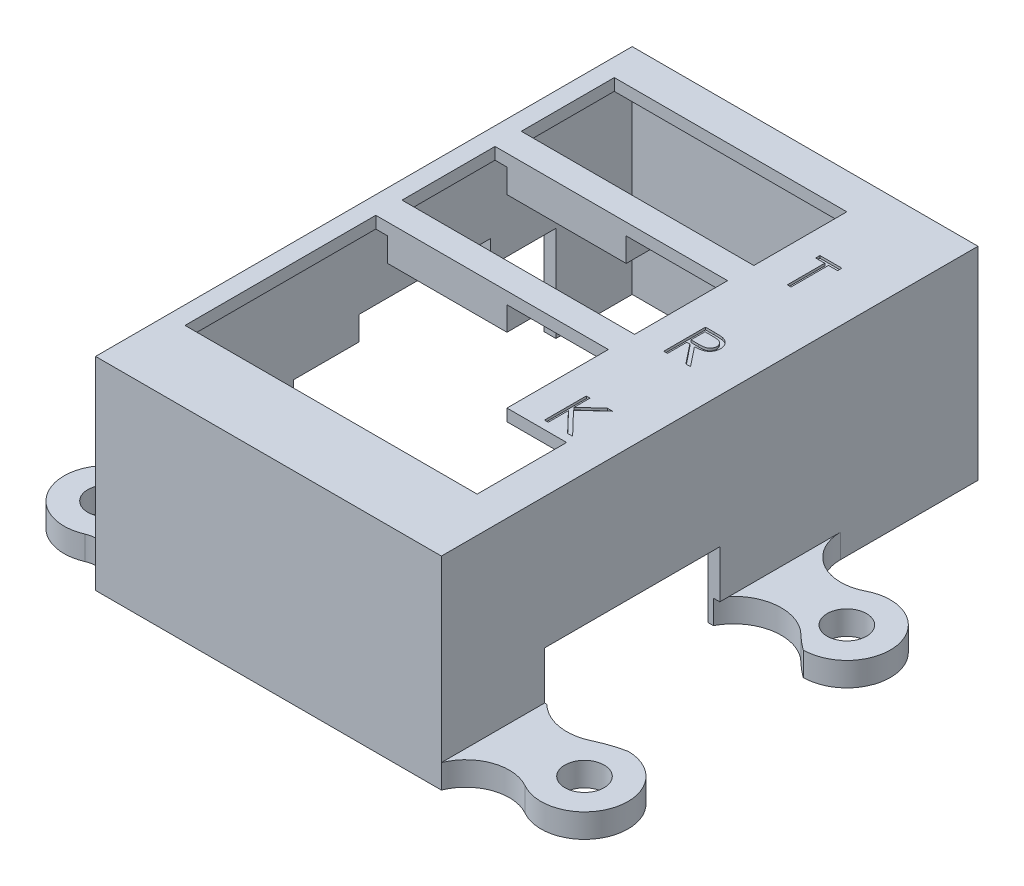
SolidWorks part; units mm, degrees
material "Polyetheretherketone (PEEK)"
ref_plane "Front Plane" through (0, 0, 0) normal (0, 0, 1) x (1, 0, 0)
ref_plane "Top Plane" through (0, 0, 0) normal (0, 1, 0) x (1, 0, 0)
ref_plane "Right Plane" through (0, 0, 0) normal (1, 0, 0) x (0, 0, -1)
sketch "Sketch1" plane through (0, 0, 0) normal (0, 1, 0) x (1, 0, 0)
  line L1 (-14.5, 22.5) -> (14.5, 22.5)
  line L2 (-14.5, 22.5) -> (-14.5, -22.5)
  line L3 (-14.5, -22.5) -> (14.5, -22.5)
  line L4 (14.5, 22.5) -> (14.5, -22.5)
  line L5 (-14.5, 22.5) -> (14.5, -22.5) construction
  line L6 (-14.5, -22.5) -> (14.5, 22.5) construction
  point P0 (0, 0)
  dimension "D1" = 45
  dimension "D2" = 29
extrude "Boss-Extrude1" add sketch "Sketch1" along normal blind 15
sketch "Sketch2" plane through (0, 15, 0) normal (0, 1, 0) x (1, 0, 0)
  line L0 (-13, 9.5) -> (-13, 1.7)
  line L1 (-13, 19.5) -> (6.5, 19.5)
  line L2 (-13, 19.5) -> (-13, 11.7)
  line L3 (-13, 11.7) -> (6.5, 11.7)
  line L4 (14.5, -22.5) -> (14.5, 22.5)
  line L5 (14.5, 22.5) -> (-14.5, 22.5)
  line L6 (-14.5, 22.5) -> (-14.5, -22.5)
  line L7 (-14.5, -22.5) -> (14.5, -22.5)
  line L8 (14.5, -22.5) -> (14.5, 22.5) construction
  line L9 (14.5, 22.5) -> (-14.5, 22.5) construction
  line L10 (-14.5, 22.5) -> (-14.5, -22.5) construction
  line L11 (-14.5, -22.5) -> (14.5, -22.5) construction
  line L12 (6.5, 19.5) -> (6.5, 11.7)
  line L13 (-13, 9.5) -> (6.5, 9.5)
  line L14 (6.5, 9.5) -> (6.5, 1.7)
  line L15 (-13, 1.7) -> (6.5, 1.7)
  line L16 (-13, -0.5) -> (-13, -8.3)
  line L17 (-13, -0.5) -> (6.5, -0.5)
  line L18 (6.5, -0.5) -> (6.5, -8.3)
  line L20 (-13, -8.3) -> (-13, -9.7)
  line L21 (6.5, -9) -> (11.5, -9)
  line L22 (-13, -9.7) -> (-13, -16.5)
  line L23 (-13, -16.5) -> (11.5, -16.5)
  line L24 (11.5, -9) -> (11.5, -16.5)
  line L25 (6.5, -8.3) -> (6.5, -9)
  line L28 (-13, -8.3) -> (6.5, -8.3) [skipped]
  dimension "D2" = 7.8
  dimension "D3" = 19.5
  dimension "D4" = 3
  dimension "D5" = 3
  dimension "D7" = 2.2
  dimension "D8" = 6.8
  dimension "D9" = 24.5
  dimension "D10" = 3
  dimension "D11" = 0.7
  dimension "D12" = 16
  dimension "D1" = 0
  dimension "D6" = 3
shell "Shell2" thickness 1 removed face at (0, 0, 0)
extrude "Cut-Extrude2" cut sketch "Sketch2" against normal through all
sketch "Sketch3" plane through (0, 14, 0) normal (0, -1, 0) x (1, 0, 0)
  line L4 (13.5, -21.5) -> (13.5, 21.5)
  line L5 (13.5, 21.5) -> (-13.5, 21.5)
  line L6 (-13.5, 21.5) -> (-13.5, -21.5)
  line L7 (-13.5, -21.5) -> (13.5, -21.5)
  line L8 (13.5, -21.5) -> (13.5, 21.5) construction
  line L9 (13.5, 21.5) -> (-13.5, 21.5) construction
  line L10 (-13.5, 21.5) -> (-13.5, -21.5) construction
  line L11 (-13.5, -21.5) -> (13.5, -21.5) construction
  line L12 (-13, -19.5) -> (6.5, -19.5)
  line L13 (-13, -11.7) -> (-13, -19.5)
  line L14 (6.5, -11.7) -> (-13, -11.7)
  line L15 (6.5, -19.5) -> (6.5, -11.7)
  line L16 (-13, -19.5) -> (6.5, -19.5) construction
  line L17 (-13, -11.7) -> (-13, -19.5) construction
  line L18 (6.5, -11.7) -> (-13, -11.7) construction
  line L19 (6.5, -19.5) -> (6.5, -11.7) construction
  line L20 (6.5, -9.5) -> (6.5, -1.7)
  line L21 (-13, -9.5) -> (6.5, -9.5)
  line L22 (-13, -1.7) -> (-13, -9.5)
  line L23 (6.5, -1.7) -> (-13, -1.7)
  line L24 (6.5, -9.5) -> (6.5, -1.7) construction
  line L25 (-13, -9.5) -> (6.5, -9.5) construction
  line L26 (-13, -1.7) -> (-13, -9.5) construction
  line L27 (6.5, -1.7) -> (-13, -1.7) construction
  line L30 (-13, 0.5) -> (6.5, 0.5)
  line L31 (-13, 16.5) -> (-13, 0.5)
  line L32 (11.5, 16.5) -> (-13, 16.5)
  line L33 (11.5, 9) -> (11.5, 16.5)
  line L34 (6.5, 9) -> (11.5, 9)
  line L35 (6.5, 0.5) -> (6.5, 9)
  line L36 (-13, 0.5) -> (6.5, 0.5) construction
  line L37 (-13, 16.5) -> (-13, 0.5) construction
  line L38 (11.5, 16.5) -> (-13, 16.5) construction
  line L39 (11.5, 9) -> (11.5, 16.5) construction
  line L40 (6.5, 9) -> (11.5, 9) construction
  line L41 (6.5, 0.5) -> (6.5, 9) construction
  line L45 (-12, 0.5) -> (-2, 0.5)
  line L46 (-12, 0.5) -> (-12, -1.7)
  line L47 (-12, -1.7) -> (-2, -1.7)
  line L48 (-2, 0.5) -> (-2, -1.7)
  line L49 (-12, -9.5) -> (-2, -9.5)
  line L50 (-12, -9.5) -> (-12, -11.7)
  line L51 (-12, -11.7) -> (-2, -11.7)
  line L52 (-2, -9.5) -> (-2, -11.7)
  dimension "D1" = 0
  dimension "D5" = 2
  dimension "D6" = 10
  dimension "D7" = 2
extrude "Boss-Extrude2" add sketch "Sketch3" along normal blind 2
sketch "cutout" plane through (-14.5, 0, 0) normal (-1, 0, 0) x (0, 0, 1)
  line L0 (-22.5, 0) -> (22.5, 0) construction
  line L1 (-15.1, 6) -> (6.9, 6)
  line L2 (-15.1, 6) -> (-15.1, 0)
  line L3 (-15.1, 0) -> (6.9, 0)
  line L4 (-22.5, 0) -> (22.5, 0)
  line L5 (22.5, 0) -> (22.5, 15)
  line L6 (22.5, 15) -> (-22.5, 15)
  line L7 (-22.5, 15) -> (-22.5, 0)
  line L8 (-22.5, 0) -> (22.5, 0) construction
  line L9 (22.5, 0) -> (22.5, 15) construction
  line L10 (22.5, 15) -> (-22.5, 15) construction
  line L11 (-22.5, 15) -> (-22.5, 0) construction
  line L12 (6.9, 6) -> (6.9, 0)
  line L14 (-9.6, 6) -> (1.4, 6)
  line L15 (-9.6, 6) -> (-9.6, 8)
  line L16 (-9.6, 8) -> (1.4, 8)
  line L17 (1.4, 6) -> (1.4, 8)
  point P14 (-4.1, 8)
  point P15 (-4.1, 6)
  line M8 (-22.5, 0) -> (22.5, 0)
  dimension "D2" = 11
  dimension "D3" = 6
  dimension "D4" = 7.4
  dimension "D5" = 22
  dimension "D6" = 2
  dimension "D1" = 0
extrude "Cut-Extrude3" cut sketch "cutout" against normal up to surface (1 mm away) contours L1 L17 L16 L15 | L12 L1 L2 M8 region at (-14.5, 3, -4.1) region at (-14.5, 7, -4.1) up to face at (-13.5, 7, 0)
sketch "Sketch5" plane through (0, 0, 0) normal (0, -1, 0) x (1, 0, 0)
  line L0 (0, 0) -> (0, 21.5) construction
  line L1 (-14.5, 6.9) -> (-14.5, 10.2084)
  line L3 (-14.5, 22.5) -> (14.5, 22.5)
  line L4 (13.5, -21.5) -> (-13.5, -21.5) construction
  line L5 (-13.5, -15.1) -> (-14.5, -15.1) construction
  line L6 (-13.5, -21.5) -> (-13.5, -15.1) construction
  line L7 (-14.5, -22.5) -> (-14.5, -15.1) construction
  line L8 (-13.5, -15.1) -> (-14.5, -15.1)
  line L9 (-13.5, -21.5) -> (-13.5, -15.1)
  line L10 (-14.5, -22.5) -> (-14.5, -15.1)
  line L11 (21.5, -0.85) -> (13.5, -0.85)
  line L12 (-14.5, 6.9) -> (-13.5, 6.9)
  line L13 (-13.5, 6.9) -> (-13.5, 21.5)
  line L14 (-13.5, 21.5) -> (13.5, 21.5)
  line L15 (13.5, 21.5) -> (13.5, -21.5)
  line L16 (13.5, -21.5) -> (-13.5, -21.5)
  line L17 (-13.5, -21.5) -> (-13.5, -15.1)
  line L18 (-13.5, -15.1) -> (-14.5, -15.1)
  line L19 (-14.5, -15.1) -> (-14.5, -22.5)
  line L20 (-14.5, -22.5) -> (14.5, -22.5)
  line L21 (14.5, -22.5) -> (14.5, 22.5)
  line L22 (14.5, 22.5) -> (-14.5, 22.5)
  line L23 (-14.5, 22.5) -> (-14.5, 6.9)
  line L24 (-14.5, 6.9) -> (-13.5, 6.9)
  line L25 (-13.5, 6.9) -> (-13.5, 21.5)
  line L26 (-13.5, 21.5) -> (13.5, 21.5)
  line L27 (13.5, 21.5) -> (13.5, 13.85)
  line L28 (13.5, -21.5) -> (-13.5, -21.5)
  line L32 (-14.5, -22.5) -> (14.5, -22.5)
  line L33 (14.5, -22.5) -> (14.5, -10.9859)
  line L34 (14.5, 22.5) -> (-14.5, 22.5)
  line L35 (-14.5, 22.5) -> (-14.5, 6.9)
  line L36 (-11.5, 6.5) -> (8.5, 6.5)
  line L37 (-11.5, 6.5) -> (-11.5, -15.5)
  line L38 (-11.5, -15.5) -> (8.5, -15.5)
  line L39 (8.5, 6.5) -> (8.5, -15.5)
  line L40 (-11.5, 6.5) -> (8.5, -15.5) construction
  line L41 (-11.5, -15.5) -> (8.5, 6.5) construction
  line L42 (21.5, 13.85) -> (13.5, 13.85)
  line L43 (13.5, 21.5) -> (13.5, -21.5) construction
  line L44 (13.5, -0.85) -> (13.5, -21.5)
  circle A0 centre (21.5, 17.5) radius 1.65
  circle A1 centre (21.5, -4.5) radius 1.65
  circle A3 centre (-18.5, 17.5) radius 1.65
  circle A4 centre (-18.5, 17.5) radius 3.65
  circle A5 centre (21.5, 17.5) radius 3.65
  circle A6 centre (21.5, -4.5) radius 3.65
  arc A8 (-17.035, 20.8431) -> (-14.5, 22.5) centre (-16.309, 22.5) ccw
  arc A11 (-14.5, 10.2084) -> (-18.325, 13.8542) centre (-18.15, 10.2084) ccw
  arc A16 (19.825, -7.743) -> (14.5, -10.9859) centre (18.15, -10.9859) ccw
  circle A18 centre (-21.5, -4.5) radius 3.65 construction
  circle A19 centre (-21.5, -4.5) radius 1.65 construction
  arc A20 (14.5, 22.5) -> (19.6963, 20.6732) centre (17.8926, 23.8464) ccw
  point P54 (-1.5, -4.5)
  line M27 (-14.5, 6.9) -> (-13.5, 6.9)
  line M28 (-13.5, 6.9) -> (-13.5, 21.5)
  line M29 (-13.5, 21.5) -> (13.5, 21.5)
  line M30 (13.5, 21.5) -> (13.5, -21.5)
  line M31 (13.5, -21.5) -> (-13.5, -21.5)
  line M32 (-13.5, -21.5) -> (-13.5, -15.1)
  line M33 (-13.5, -15.1) -> (-14.5, -15.1)
  line M34 (-14.5, -15.1) -> (-14.5, -22.5)
  line M35 (-14.5, -22.5) -> (14.5, -22.5)
  line M36 (14.5, -22.5) -> (14.5, 22.5)
  line M37 (14.5, 22.5) -> (-14.5, 22.5)
  line M38 (-14.5, 22.5) -> (-14.5, 6.9)
  dimension "D1" = 0
  dimension "D2" = 3.3
  dimension "D3" = 3.3
  dimension "D4" = 7
  dimension "D5" = 5
  dimension "D6" = 22
  dimension "D9" = 20
  dimension "D10" = 4
  dimension "D11" = 5
  dimension "D12" = 27
  dimension "D13" = 43
  dimension "D14" = 5
  dimension "D15" = 6
  dimension "D8" = 15
  dimension "D16" = 17
extrude "Boss-Extrude3" add sketch "Sketch5" along normal blind 2 contours A4 A3 | A11 A8 A4 M38 | L26 L33 M38 M27 M28 M29 M30 M31 M32 M33 M34 M35 M36 M37 | A5 M36 | A5 A0 | L33 A16 A6 | A6 A1 | L42 M36 M37 M38 M27 M28 M29 M30 region at (-14.1707, 0, 8.5542) region at (-15.5429, 0, 12.9437) region at (-21.9878, 0, 18.1438) region at (16.4492, 0, 17.1799) region at (23.2837, 0, 20.5656) region at (14.1381, 0, -5.918) region at (16.43, 0, -4.3695) region at (24.0079, 0, -1.9921)
sketch "Sketch6" plane through (0, 15, 0) normal (0, 1, 0) x (1, 0, 0)
  line L3 (8.5, 11.7) -> (13.4782, 11.7) construction
  line L7 (8.5, 1.7) -> (12.8749, 1.7) construction
  line L11 (8.5, -8.3) -> (12.5892, -8.3) construction
  line L16 (6.5, 9.5) -> (-13, 9.5)
  line L17 (6.5, 1.7) -> (6.5, 9.5)
  line L18 (-13, 1.7) -> (6.5, 1.7)
  line L19 (-13, 9.5) -> (-13, 1.7)
  line L20 (6.5, 9.5) -> (-13, 9.5) construction
  line L21 (6.5, 1.7) -> (6.5, 9.5) construction
  line L22 (-13, 1.7) -> (6.5, 1.7) construction
  line L23 (-13, 9.5) -> (-13, 1.7) construction
  line L24 (-13, 19.5) -> (-13, 11.7)
  line L25 (6.5, 19.5) -> (-13, 19.5)
  line L26 (-13, -0.5) -> (-13, -16.5)
  line L27 (6.5, -0.5) -> (-13, -0.5)
  line L28 (6.5, -9) -> (6.5, -0.5)
  line L29 (11.5, -9) -> (6.5, -9)
  line L30 (11.5, -16.5) -> (11.5, -9)
  line L31 (-13, -16.5) -> (11.5, -16.5)
  line L32 (-13, -0.5) -> (-13, -16.5) construction
  line L33 (6.5, -0.5) -> (-13, -0.5) construction
  line L34 (6.5, -9) -> (6.5, -0.5) construction
  line L35 (11.5, -9) -> (6.5, -9) construction
  line L36 (11.5, -16.5) -> (11.5, -9) construction
  line L37 (-13, -16.5) -> (11.5, -16.5) construction
  line L38 (6.5, 11.7) -> (6.5, 19.5)
  line L39 (-13, 11.7) -> (6.5, 11.7)
  line L40 (-13, 19.5) -> (-13, 11.7) construction
  line L41 (6.5, 19.5) -> (-13, 19.5) construction
  line L42 (6.5, 11.7) -> (6.5, 19.5) construction
  line L43 (-13, 11.7) -> (6.5, 11.7) construction
  text T0 "T"
  text T1 "R"
  text T2 "K"
  dimension "D1" = 0
  dimension "D2" = 0
  dimension "D4" = 10
  dimension "D5" = 2
  dimension "D3" = 0
extrude "Cut-Extrude4" cut sketch "Sketch6" against normal blind 0.2
sketch "Sketch7" plane through (14.5, 0, 0) normal (1, 0, 0) x (0, 0, -1)
  line L1 (-13.85, 4) -> (0.85, 4)
  line L2 (-13.85, 4) -> (-13.85, 0)
  line L3 (-13.85, 0) -> (0.85, 0)
  line L4 (0.85, 4) -> (0.85, 0)
  line L8 (-22.5, 0) -> (-13.85, 0)
  line L9 (-13.85, 0) -> (0.85, 0)
  line L10 (0.85, 0) -> (10.9859, 0)
  line L11 (10.9859, 0) -> (10.9859, -2)
  line L12 (10.9859, -2) -> (22.5, -2)
  line L13 (22.5, -2) -> (22.5, 15)
  line L14 (22.5, 15) -> (-22.5, 15)
  line L15 (-22.5, 15) -> (-22.5, 0)
  line L16 (-22.5, 0) -> (-13.85, 0)
  line L17 (-13.85, 0) -> (0.85, 0)
  line L18 (0.85, 0) -> (10.9859, 0)
  line L19 (10.9859, 0) -> (10.9859, -2)
  line L20 (10.9859, -2) -> (22.5, -2)
  line L21 (22.5, -2) -> (22.5, 15)
  line L22 (22.5, 15) -> (-22.5, 15)
  line L23 (-22.5, 15) -> (-22.5, 0)
  line M14 (-13.85, 0) -> (0.85, 0)
  dimension "D2" = 4
  dimension "D1" = 0
extrude "Cut-Extrude5" cut sketch "Sketch7" against normal up to surface (1 mm away) contours L4 L1 L2 M14 region at (14.5, 2, 6.5)
sketch "Sketch8" plane through (0, 0, 0) normal (0, 1, 0) x (1, 0, 0)
  line L0 (14.5, 10.9859) -> (14.5, 0.85) construction
  line L1 (14.5, 0.85) -> (21.5, 0.85) construction
  line L2 (21.5, -13.85) -> (14.5, -13.85) construction
  line L3 (14.5, -13.85) -> (14.5, -22.5) construction
  line L4 (14.5, 10.9859) -> (14.5, 0.85)
  line L5 (14.5, 0.85) -> (21.5, 0.85)
  line L6 (21.5, -13.85) -> (14.5, -13.85)
  line L7 (14.5, -13.85) -> (14.5, -22.5)
  arc A0 (21.5, 0.85) -> (19.825, 7.743) centre (21.5, 4.5) ccw construction
  arc A1 (14.5, 10.9859) -> (19.825, 7.743) centre (18.15, 10.9859) ccw construction
  arc A2 (19.6963, -20.6732) -> (14.5, -22.5) centre (17.8926, -23.8464) ccw construction
  arc A3 (19.6963, -20.6732) -> (21.5, -13.85) centre (21.5, -17.5) ccw construction
  arc A4 (21.5, 0.85) -> (19.825, 7.743) centre (21.5, 4.5) ccw
  arc A5 (14.5, 10.9859) -> (19.825, 7.743) centre (18.15, 10.9859) ccw
  arc A6 (19.6963, -20.6732) -> (14.5, -22.5) centre (17.8926, -23.8464) ccw
  arc A7 (19.6963, -20.6732) -> (21.5, -13.85) centre (21.5, -17.5) ccw
  circle A8 centre (17.5, -1) radius 4
  circle A9 centre (17.5, -11) radius 4
  dimension "D1" = 10
  dimension "D4" = 8
  dimension "D2" = 4
  dimension "D3" = 5.5
extrude "Cut-Extrude6" cut sketch "Sketch8" against normal blind 10 contours L6 A9 | L6 A9 | L4 A8 L5 | L5 A8 L4 region at (17.5708, 0, -1.747) region at (17.481, 0, 1.7378) region at (17.5, 0, 14.3162) region at (17.5, 0, 10.6783)
fillet "Fillet1" radius 10 2 edges at (21.0465, -1, -0.85) (20.3067, -1, 13.85)
equation "\"D4@Sketch2\"=\"D5@Sketch2\""
equation "\"D10@Sketch2\"=\"D5@Sketch2\""
equation "\"D7@Sketch3\"=\"D5@Sketch3\""
equation "\"D3@Sketch5\"=\"D2@Sketch5\""
equation "\"D11@Sketch5\"=\"D5@Sketch5\""
